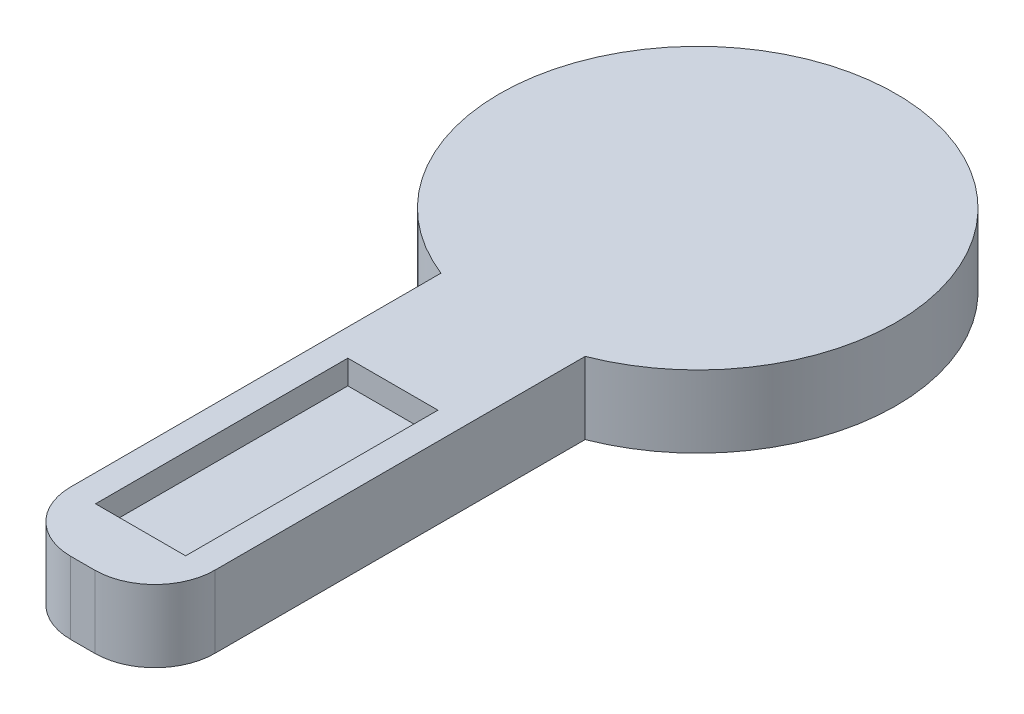
SolidWorks part; units mm, degrees
ref_plane "Front Plane" through (0, 0, 0) normal (0, 0, 1) x (1, 0, 0)
ref_plane "Top Plane" through (0, 0, 0) normal (0, 1, 0) x (1, 0, 0)
ref_plane "Right Plane" through (0, 0, 0) normal (1, 0, 0) x (0, 0, -1)
sketch "Sketch1" plane through (0, 0, 0) normal (0, 1, 0) x (1, 0, 0)
  line L0 (0, 93.9283) -> (0, -81.1352) construction
  line L3 (-6, 30) -> (6, 30)
  line L4 (-6, 30) -> (-6, -30)
  line L5 (-6, -30) -> (6, -30)
  line L6 (6, 30) -> (6, -30)
  line L7 (-64.9755, 0) -> (70.6987, 0) construction
  dimension "D2" = 60
  dimension "D1" = 12
extrude "Boss-Extrude1" add sketch "Sketch1" along normal blind 6
sketch "Sketch2" plane through (0, 6, 0) normal (0, 1, 0) x (1, 0, 0)
  line L0 (-13.6791, 21.185) -> (20.5769, 21.185) construction
  line L1 (-1.7496, 24.0066) -> (1.7496, 24.0066) construction
  line L2 (-1.7496, 24.0066) -> (-1.7496, 18.3634) construction
  line L3 (-1.7496, 18.3634) -> (1.7496, 18.3634) construction
  line L4 (1.7496, 24.0066) -> (1.7496, 18.3634) construction
  line L5 (-3.75, -4.185) -> (3.75, -4.185)
  line L6 (-3.75, -4.185) -> (-3.75, -25.185)
  line L7 (-3.75, -25.185) -> (3.75, -25.185)
  line L8 (3.75, -4.185) -> (3.75, -25.185)
  line L9 (-8.165, -21.185) -> (28.578, -21.185) construction
  line L10 (-24.9724, 0) -> (40.7727, 0) construction
  line L11 (0, 33.6512) -> (0, -35.6142) construction
  line L13 (-6, -30) -> (6, -30) construction
  circle A0 centre (0, -21.185) radius 3.5 construction
  dimension "D5" = 7
  dimension "D6" = 0.5
  dimension "D1" = 42.37
  dimension "D2" = 21.185
  dimension "D3" = 7.5
  dimension "D4" = 21
  dimension "D7" = 8.815
extrude "Cut-Extrude1" cut sketch "Sketch2" against normal blind 2
sketch "Sketch4" plane through (0, 0, 0) normal (0, -1, 0) x (1, 0, 0)
  line L1 (0, 0) -> (0, 36.451) construction
  line L2 (-6, 30) -> (6, 30) construction
  circle A0 centre (0, 21.18) radius 3.5
  point P2 (0, 22.0386)
  dimension "D1" = 7
  dimension "D2" = 8.82
extrude "Boss-Extrude2" add sketch "Sketch4" along normal blind 1
sketch "Sketch5" plane through (0, 6, 0) normal (0, 1, 0) x (1, 0, 0)
  line L0 (0, 0) -> (0, 39.3701) construction
  circle A0 centre (0, 21.19) radius 16.5
  dimension "D2" = 33
  dimension "D1" = 21.19
extrude "Boss-Extrude3" add sketch "Sketch5" against normal blind 6
fillet "Fillet2" radius 5 2 edges at (6, 3, 30) (-6, 3, 30)
